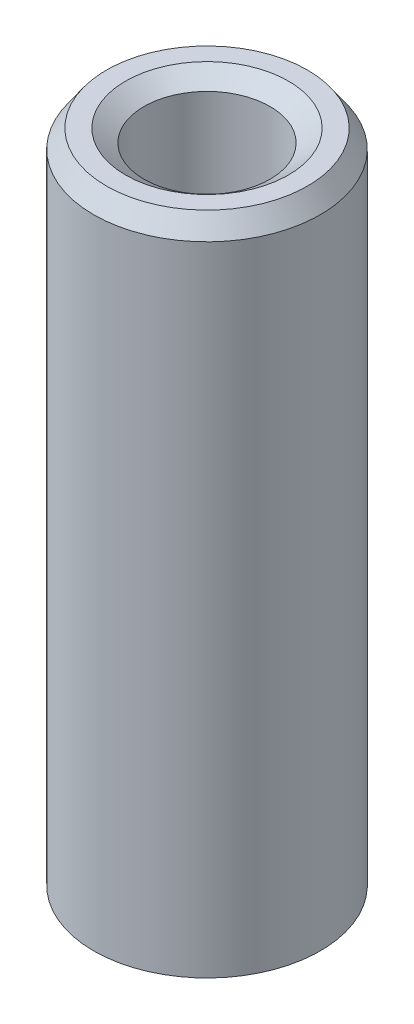
SolidWorks part; units mm, degrees
ref_plane "Front Plane" through (0, 0, 0) normal (0, 0, 1) x (1, 0, 0)
ref_plane "Top Plane" through (0, 0, 0) normal (0, 1, 0) x (1, 0, 0)
ref_plane "Right Plane" through (0, 0, 0) normal (1, 0, 0) x (0, 0, -1)
sketch "Sketch1" plane through (0, 0, 0) normal (0, 1, 0) x (1, 0, 0)
  circle A0 centre (0, 0) radius 22.5
  dimension "SLEEVE_OD" = 45
extrude "Boss-Extrude1" add sketch "Sketch1" along normal blind 132.7398
sketch "Sketch2" plane through (0, 0, 0) normal (0, 1, 0) x (1, 0, 0)
  circle A0 centre (0, 0) radius 12.5141
  dimension "BORE_D" = 25.0282
extrude "Cut-Extrude1" cut sketch "Sketch2" along normal through all
chamfer "Chamfer1" distance 3.6495 angle 34.896 4 edges at (0, 132.7398, 12.5141) (0, 0, 12.5141) (0, 0, 22.5) (0, 132.7398, 22.5) first distance on face at (0, 132.7398, 12.5141) first distance on face at (0, 0, 12.5141) first distance on face at (0, 132.7398, 22.5)
